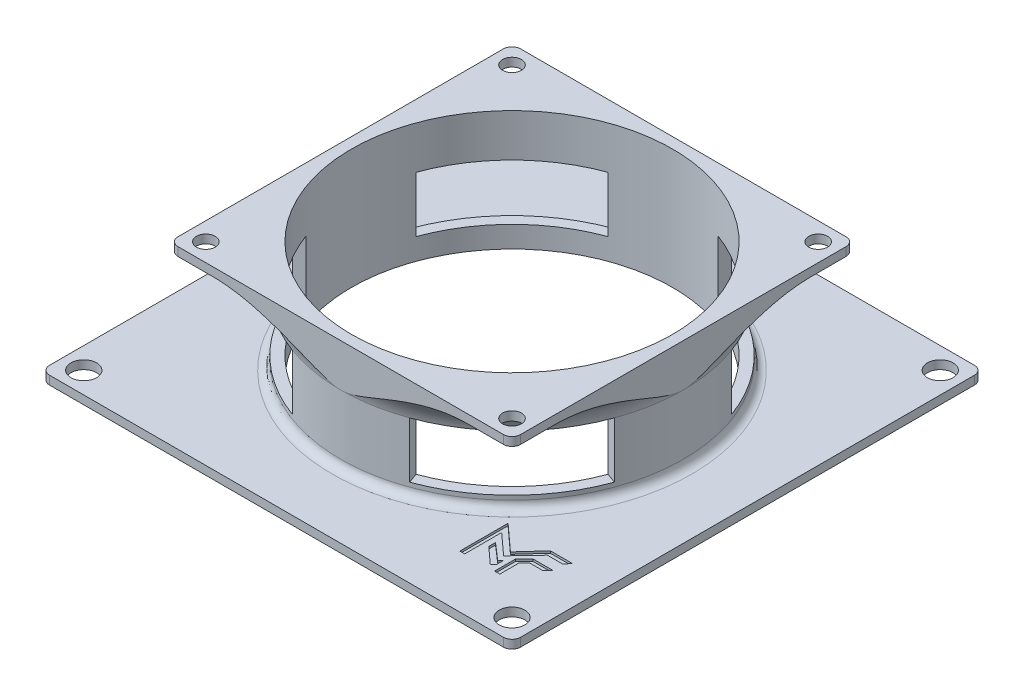
SolidWorks part; units mm, degrees
ref_plane "Plano frontal" through (0, 0, 0) normal (0, 0, 1) x (1, 0, 0)
ref_plane "Plano superior" through (0, 0, 0) normal (0, 1, 0) x (1, 0, 0)
ref_plane "Plano direito" through (0, 0, 0) normal (1, 0, 0) x (0, 0, -1)
sketch "Esboço1" plane through (0, 0, 0) normal (0, 1, 0) x (1, 0, 0)
  line L0 (0, 0) -> (19.0251, 0) construction
  line L1 (-55, -55) -> (55, -55)
  line L2 (-55, -55) -> (-55, 55)
  line L3 (-55, 55) -> (55, 55)
  line L4 (55, -55) -> (55, 55)
  line L5 (-55, -55) -> (55, 55) construction
  line L6 (-55, 55) -> (55, -55) construction
  line L7 (-55, -50) -> (-50, -50) construction
  line L8 (-55, -50) -> (-55, -55) construction
  line L9 (-55, -55) -> (-50, -55) construction
  line L10 (-50, -50) -> (-50, -55) construction
  line L11 (-55, -50) -> (-50, -55) construction
  line L12 (-55, -55) -> (-50, -50) construction
  line L13 (0, 0) -> (0, -21.9062) construction
  circle A0 centre (-50, -50) radius 3
  circle A1 centre (50, -50) radius 3
  circle A2 centre (50, 50) radius 3
  circle A3 centre (-50, 50) radius 3
  point P0 (0, 0)
  point P10 (-52.5, -52.5)
  dimension "D3" = 6
  dimension "D1" = 110
  dimension "D2" = 5
extrude "Ressalto-extrusão1" add sketch "Esboço1" against normal blind 2
sketch "Esboço2" plane through (0, 0, 0) normal (0, 1, 0) x (1, 0, 0)
  circle A0 centre (0, 0) radius 37.5
  dimension "D1" = 75
extrude "Corte-extrusão1" cut sketch "Esboço2" against normal blind 2
sketch "Logo_MF" plane through (0, 0, 0) normal (0, 1, 0) x (1, 0, 0)
  line L0 (129.3873, -24.035) -> (965.3873, -24.035) construction
  line L1 (30.4814, -42.65) -> (31.615, -42.65)
  line L2 (31.615, -42.65) -> (31.615, -34.0301)
  line L3 (31.615, -34.0301) -> (36.554, -38.5166)
  line L4 (36.554, -38.5166) -> (41.537, -33.2737)
  line L5 (41.537, -33.2737) -> (45.0559, -33.2737)
  line L6 (45.0559, -33.2737) -> (46.1839, -32.032)
  line L7 (46.1839, -32.032) -> (40.9934, -32.032)
  line L8 (40.9934, -32.032) -> (36.5558, -36.9172)
  line L9 (36.5558, -36.9172) -> (30.4814, -31.3993)
  line L10 (30.4814, -31.3993) -> (30.4814, -42.65)
  line L11 (32.9236, -36.7693) -> (32.9236, -38.3398)
  line L12 (32.9236, -38.3398) -> (36.8041, -41.8647)
  line L13 (36.8041, -41.8647) -> (37.485, -41.1152)
  line L14 (37.485, -41.1152) -> (37.485, -39.395)
  line L15 (37.485, -39.395) -> (36.8029, -40.1458)
  line L16 (36.8029, -40.1458) -> (32.9236, -36.7693)
  line L17 (38.585, -42.65) -> (38.585, -37.808)
  line L18 (38.585, -37.808) -> (40.585, -35.7037)
  line L19 (40.585, -35.7037) -> (45.2684, -35.7037)
  line L20 (45.2684, -35.7037) -> (44.1161, -36.9162)
  line L21 (44.1161, -36.9162) -> (40.9939, -36.9162)
  line L22 (40.9939, -36.9162) -> (39.8, -38.1723)
  line L23 (39.8, -38.1723) -> (39.8, -42.65)
  line L24 (39.8, -42.65) -> (38.585, -42.65)
  line L25 (-55, -55) -> (55, -55) construction
  circle A0 centre (50, -50) radius 3 construction
  circle A1 centre (-50, -50) radius 3 construction
  dimension "D4" = 10.2
  dimension "D1" = 2.43
  dimension "D2" = 6.97
  dimension "D3" = 1.1
  dimension "D5" = 12.35
  dimension "D6" = 80.4814
  dimension "D7" = 81.615
  dimension "D8" = 82.9236
  dimension "D9" = 86.554
  dimension "D10" = 86.5558
  dimension "D11" = 86.8029
  dimension "D12" = 86.8041
  dimension "D13" = 87.485
  dimension "D14" = 8.1353
  dimension "D15" = 90.585
  dimension "D16" = 90.9934
  dimension "D17" = 90.9939
  dimension "D18" = 91.537
  dimension "D19" = 94.1161
  dimension "D20" = 95.0559
  dimension "D21" = 95.2684
  dimension "D22" = 96.1839
  dimension "D23" = 8.8848
  dimension "D24" = 9.8542
  dimension "D25" = 11.4834
  dimension "D26" = 11.8277
  dimension "D32" = 13.2307
extrude "Corte-extrusão2" cut sketch "Logo_MF" against normal blind 0.5
sketch "Esboço4" plane through (0, 0, 0) normal (0, 1, 0) x (1, 0, 0)
  circle A0 centre (0, 0) radius 37.5 construction
  circle A1 centre (0, 0) radius 37.5
  circle A2 centre (0, 0) radius 40
  dimension "D1" = 2.5
extrude "Ressalto-extrusão2" add sketch "Esboço4" along normal blind 3
sketch "Esboço5" plane through (0, 3, 0) normal (0, 1, 0) x (1, 0, 0)
  line L0 (0, 0) -> (0, 55) construction
  line L1 (55, 55) -> (-55, 55) construction
  line L2 (0, 0) -> (-21.0935, 57.954)
  line L3 (0, 0) -> (21.3584, 58.6817)
  line L4 (0, 0) -> (57.954, 21.0935)
  line L5 (0, 0) -> (58.6817, -21.3584)
  line L6 (0, 0) -> (21.0935, -57.954)
  line L7 (0, 0) -> (-21.3584, -58.6817)
  line L8 (0, 0) -> (-57.954, -21.0935)
  line L9 (0, 0) -> (-58.6817, 21.3584)
  point P16 (0, 0)
  circle M5 centre (0, 0) radius 40
  circle M6 centre (0, 0) radius 37.5
  dimension "D1" = 20
  dimension "D2" = 20
  dimension "D3" = 4
extrude "Ressalto-extrusão3" add sketch "Esboço5" along normal blind 13 contours L0 L3 M6 M5 | L0 L2 M6 M5 | L9 L8 M6 M5 | L7 L6 M6 M5 | L5 L4 M6 M5 region at (-6.6971, 3, -37.981) region at (6.6971, 3, -37.981) region at (37.981, 3, 0) region at (0, 3, 37.981) region at (-37.981, 3, 0)
sketch "Esboço6" plane through (0, 16, 0) normal (0, 1, 0) x (1, 0, 0)
  arc A0 (12.8258, 35.2385) -> (-12.8258, 35.2385) centre (0, 0) ccw construction
  arc A1 (35.2385, 12.8258) -> (12.8258, 35.2385) centre (0, 0) ccw construction
  arc A2 (35.2385, -12.8258) -> (35.2385, 12.8258) centre (0, 0) ccw construction
  arc A3 (12.8258, -35.2385) -> (35.2385, -12.8258) centre (0, 0) ccw construction
  arc A4 (-12.8258, -35.2385) -> (12.8258, -35.2385) centre (0, 0) ccw construction
  arc A5 (-35.2385, -12.8258) -> (-12.8258, -35.2385) centre (0, 0) ccw construction
  arc A6 (-35.2385, 12.8258) -> (-35.2385, -12.8258) centre (0, 0) ccw construction
  arc A7 (-12.8258, 35.2385) -> (-35.2385, 12.8258) centre (0, 0) ccw construction
  arc A8 (12.8258, 35.2385) -> (-12.8258, 35.2385) centre (0, 0) ccw
  arc A9 (35.2385, 12.8258) -> (12.8258, 35.2385) centre (0, 0) ccw
  arc A10 (35.2385, -12.8258) -> (35.2385, 12.8258) centre (0, 0) ccw
  arc A11 (12.8258, -35.2385) -> (35.2385, -12.8258) centre (0, 0) ccw
  arc A12 (-12.8258, -35.2385) -> (12.8258, -35.2385) centre (0, 0) ccw
  arc A13 (-35.2385, -12.8258) -> (-12.8258, -35.2385) centre (0, 0) ccw
  arc A14 (-35.2385, 12.8258) -> (-35.2385, -12.8258) centre (0, 0) ccw
  arc A15 (-12.8258, 35.2385) -> (-35.2385, 12.8258) centre (0, 0) ccw
  circle A16 centre (0, 0) radius 40 construction
  circle A17 centre (0, 0) radius 40
extrude "Ressalto-extrusão4" add sketch "Esboço6" along normal blind 8
sketch "Esboço7" plane through (0, 24, 0) normal (0, 1, 0) x (1, 0, 0)
  line L0 (0, 0) -> (0, -15.2135) construction
  line L1 (-40, 40) -> (40, 40)
  line L2 (-40, 40) -> (-40, -40)
  line L3 (-40, -40) -> (40, -40)
  line L4 (40, 40) -> (40, -40)
  line L5 (-40, 40) -> (40, -40) construction
  line L6 (-40, -40) -> (40, 40) construction
  line L7 (-40, -35.75) -> (-35.75, -35.75) construction
  line L8 (-40, -35.75) -> (-40, -40) construction
  line L9 (-40, -40) -> (-35.75, -40) construction
  line L10 (-35.75, -35.75) -> (-35.75, -40) construction
  line L11 (-40, -35.75) -> (-35.75, -40) construction
  line L12 (-40, -40) -> (-35.75, -35.75) construction
  line L13 (0, 0) -> (13.3815, 0) construction
  circle A0 centre (0, 0) radius 37.5 construction
  circle A1 centre (0, 0) radius 37.5
  circle A2 centre (-35.75, -35.75) radius 2.2
  circle A3 centre (35.75, -35.75) radius 2.2
  circle A4 centre (35.75, 35.75) radius 2.2
  circle A5 centre (-35.75, 35.75) radius 2.2
  point P9 (-37.875, -37.875)
  dimension "D3" = 4.4
  dimension "D1" = 80
  dimension "D2" = 4.25
extrude "Ressalto-extrusão5" add sketch "Esboço7" along normal blind 2
fillet "Filete1" radius 2 8 edges at (-40, 25, -40) (-40, 25, 40) (40, 25, 40) (40, 25, -40) (55, -1, -55) (-55, -1, -55) (-55, -1, 55) (55, -1, 55)
fillet "Filete2" radius 2 1 edges at (0, 0, -40)
fillet "Filete3" radius 10 4 edges at (28.2843, 24, -28.2843) (28.2843, 24, 28.2843) (-28.2843, 24, 28.2843) (-28.2843, 24, -28.2843)
equation "\"D2@Esboço5\"=\"D1@Esboço5\""
